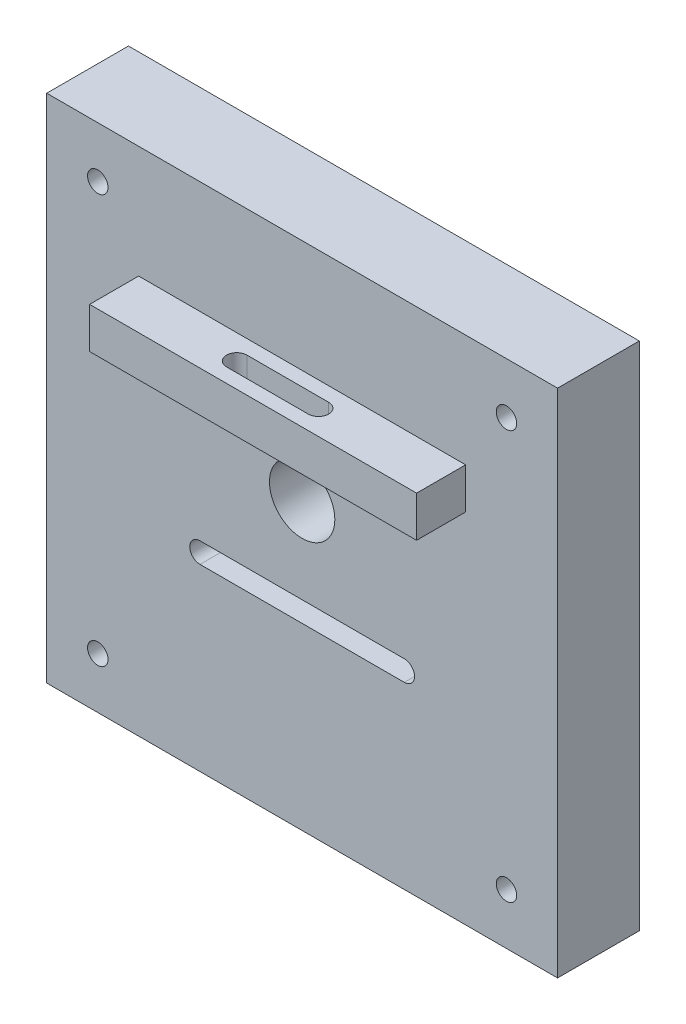
SolidWorks part; units mm, degrees
ref_plane "Front Plane" through (0, 0, 0) normal (0, 0, 1) x (1, 0, 0)
ref_plane "Top Plane" through (0, 0, 0) normal (0, 1, 0) x (1, 0, 0)
ref_plane "Right Plane" through (0, 0, 0) normal (1, 0, 0) x (0, 0, -1)
sketch "Sketch1" plane through (0, 0, 0) normal (0, 0, 1) x (1, 0, 0)
  line L1 (-58.3251, 63.7279) -> (66.6749, 63.7279)
  line L2 (-58.3251, 63.7279) -> (-58.3251, -61.2721)
  line L3 (-58.3251, -61.2721) -> (66.6749, -61.2721)
  line L4 (66.6749, 63.7279) -> (66.6749, -61.2721)
  dimension "D1" = 125
  dimension "D2" = 125
extrude "Boss-Extrude1" add sketch "Sketch1" along normal blind 20
sketch "Sketch2" plane through (0, 0, 20) normal (0, 0, 1) x (1, 0, 0)
  line L0 (-58.3251, 63.7279) -> (-58.3251, -61.2721) construction
  line L1 (66.6749, 63.7279) -> (-58.3251, 63.7279) construction
  circle A0 centre (-45.8251, 51.2279) radius 2.5
  circle A1 centre (54.1749, 51.2279) radius 2.5
  circle A2 centre (54.1749, -48.7721) radius 2.5
  circle A3 centre (-45.8251, -48.7721) radius 2.5
  dimension "D1" = 5
  dimension "D2" = 12.5
  dimension "D3" = 12.5
  dimension "D4" = 2
  dimension "D5" = 2
extrude "Cut-Extrude1" cut sketch "Sketch2" against normal through all
sketch "Sketch3" plane through (0, 0, 20) normal (0, 0, 1) x (1, 0, 0)
  line L0 (-58.3251, 63.7279) -> (-58.3251, -61.2721) construction
  line L1 (-35.8251, 26.2279) -> (44.1749, 26.2279) construction
  line L2 (-35.8251, 26.2279) -> (-35.8251, -23.7721) construction
  line L3 (-35.8251, -23.7721) -> (44.1749, -23.7721) construction
  line L4 (44.1749, 26.2279) -> (44.1749, -23.7721) construction
  line L5 (66.6749, 63.7279) -> (-58.3251, 63.7279) construction
  line L6 (-35.8251, -14.8721) -> (-16.8951, -14.8721) construction
  line L7 (4.1749, 26.2279) -> (4.1749, -12.3721) construction
  line L8 (-20.8251, -12.3721) -> (29.1749, -12.3721)
  line L10 (29.1749, -17.3721) -> (-20.8251, -17.3721)
  line L11 (4.1749, -14.8721) -> (44.1749, -14.8721) construction
  line L12 (4.1749, -17.3721) -> (4.1749, -23.7721) construction
  arc A0 (-20.8251, -12.3721) -> (-20.8251, -17.3721) centre (-20.8251, -14.8721) ccw
  arc A1 (29.1749, -12.3721) -> (29.1749, -17.3721) centre (29.1749, -14.8721) cw
  circle A2 centre (4.1749, 8.6279) radius 8
  point P4 (-58.3251, 1.2279)
  point P7 (-35.8251, 1.2279)
  point P8 (4.1749, 26.2279)
  point P11 (4.1749, 63.7279)
  dimension "D4" = 5
  dimension "D7" = 16
  dimension "D1" = 80
  dimension "D2" = 50
  dimension "D3" = 8.9
  dimension "D5" = 15
  dimension "D6" = 17.6
extrude "Cut-Extrude2" cut sketch "Sketch3" against normal through all
sketch "Sketch4" plane through (0, 0, 0) normal (0, 0, -1) x (-1, 0, 0)
  line L0 (-29.1749, -12.3721) -> (20.8251, -12.3721) construction
  line L1 (-39.1749, -7.3721) -> (30.8251, -7.3721)
  line L2 (-39.1749, -7.3721) -> (-39.1749, -22.3721)
  line L3 (-39.1749, -22.3721) -> (30.8251, -22.3721)
  line L4 (30.8251, -7.3721) -> (30.8251, -22.3721)
  arc A0 (-29.1749, -12.3721) -> (-29.1749, -17.3721) centre (-29.1749, -14.8721) ccw construction
  point P4 (-4.1749, -7.3721)
  point P7 (-4.1749, -12.3721)
  point P11 (-31.6749, -14.8721)
  point P12 (-39.1749, -14.8721)
  dimension "D1" = 15
  dimension "D2" = 70
extrude "Cut-Extrude3" cut sketch "Sketch4" against normal blind 10
fillet "Fillet1" radius 5 4 edges at (-30.8251, -22.3721, 5) (39.1749, -22.3721, 5) (-30.8251, -7.3721, 5) (39.1749, -7.3721, 5)
sketch "Sketch6" plane through (0, 0, 20) normal (0, 0, 1) x (1, 0, 0)
  line L1 (-35.8251, 26.2279) -> (44.1749, 26.2279) construction
  line L2 (-35.8251, 26.2279) -> (-35.8251, -23.7721) construction
  line L3 (-35.8251, -23.7721) -> (44.1749, -23.7721) construction
  line L4 (44.1749, 26.2279) -> (44.1749, -23.7721) construction
  line L6 (-35.8251, -14.8721) -> (-16.8951, -14.8721) construction
  line L7 (4.1749, 26.2279) -> (4.1749, -12.3721) construction
  line L11 (4.1749, -14.8721) -> (44.1749, -14.8721) construction
  line L12 (4.1749, -17.3721) -> (4.1749, -23.7721) construction
  line L13 (-58.3251, -61.2721) -> (66.6749, -61.2721) construction
  line L14 (-58.3251, 63.7279) -> (-58.3251, -61.2721) construction
  line L16 (-35.8251, 26.2279) -> (44.1749, 26.2279)
  line L17 (-35.8251, 26.2279) -> (-35.8251, 36.2279)
  line L18 (-35.8251, 36.2279) -> (44.1749, 36.2279)
  line L19 (44.1749, 26.2279) -> (44.1749, 36.2279)
  point P4 (0, 0)
  point P7 (-35.8251, 1.2279)
  point P8 (4.1749, 26.2279)
  point P10 (4.1749, -61.2721)
  point P29 (-58.3251, 1.2279)
  dimension "D4" = 10
  dimension "D1" = 80
  dimension "D2" = 50
  dimension "D3" = 8.9
extrude "Boss-Extrude2" add sketch "Sketch6" along normal blind 12
sketch "Sketch7" plane through (0, 36.2279, 0) normal (0, 1, 0) x (1, 0, 0)
  line L0 (-35.8251, -26) -> (44.1749, -26) construction
  line L1 (-35.8251, -32) -> (-35.8251, -20) construction
  line L2 (44.1749, -32) -> (44.1749, -20) construction
  line L3 (4.1749, -20) -> (4.1749, -32) construction
  line L4 (44.1749, -20) -> (-35.8251, -20) construction
  line L5 (44.1749, -32) -> (-35.8251, -32) construction
  line L6 (-5.8251, -28.5) -> (14.1749, -28.5)
  line L7 (-5.8251, -23.5) -> (14.1749, -23.5)
  arc A0 (-5.8251, -23.5) -> (-5.8251, -28.5) centre (-5.8251, -26) ccw
  arc A1 (14.1749, -23.5) -> (14.1749, -28.5) centre (14.1749, -26) cw
  dimension "D1" = 5
  dimension "D2" = 30
extrude "Cut-Extrude4" cut sketch "Sketch7" against normal through all
